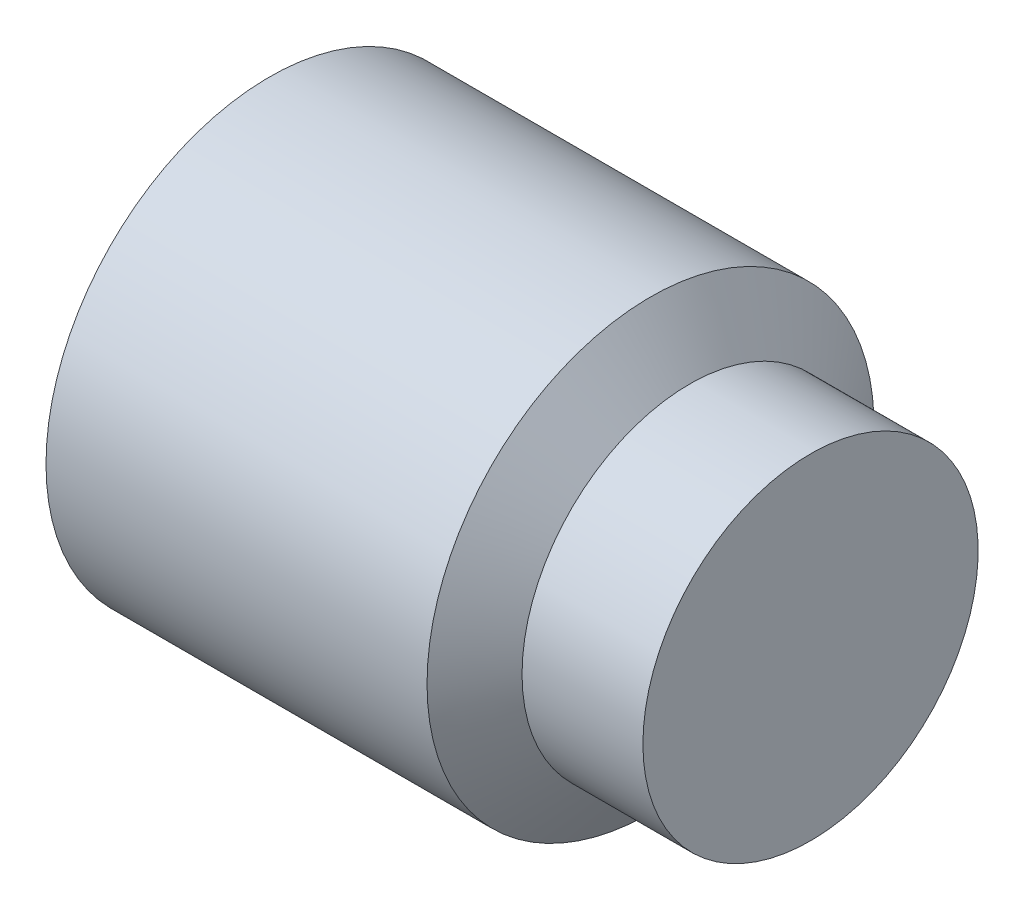
SolidWorks part; units mm, degrees
revolve "BaseBody" add sketch "BodySke" angle 360 about L5 other way angle 60
sketch "BodySke" plane through (0, 0, 0) normal (0, 0, 1) x (1, 0, 0)
  line L0 (0, 0) -> (0, 10.352)
  line L1 (0, 10.352) -> (0.9515, 12)
  line L2 (0.9515, 12) -> (21.4094, 12)
  line L3 (21.4094, 12) -> (23.51, 9)
  line L4 (30, 0) -> (0, 0)
  line L5 (-12.7, 0) -> (88.9, 0) construction
  line L6 (23.51, 9) -> (30, 9)
  line L7 (30, 9) -> (30, 0)
  line L8 (0, -10.352) -> (0.9515, -12) construction
  line L9 (23.51, -9) -> (30, -9) construction
  line L10 (3, 15.875) -> (3, -3.175) construction
  dimension "Length" = 30
  dimension "D1" = 35
  dimension "Diameter" = 24
cosmetic thread "ThreadCosmetic" [suppressed] parameters "Thread_minor"=20.704
ref_plane "Plane1" through (0, 0, 0) normal (0, 0, 1) x (1, 0, 0)
ref_plane "Plane2" through (0, 0, 0) normal (0, 1, 0) x (1, 0, 0)
ref_plane "Plane3" through (0, 0, 0) normal (1, 0, 0) x (0, 0, -1)
sketch "Sketch2" plane through (0, 0, 0) normal (-1, 0, 0) x (0, 0, 1)
  line L0 (3.4641, 6) -> (-3.4641, 6)
  line L1 (-3.4641, 6) -> (-6.9282, 0)
  line L2 (3.4641, 6) -> (6.9282, 0)
  line L3 (3.4641, -6) -> (6.9282, 0)
  line L4 (3.4641, -6) -> (-3.4641, -6)
  line L5 (-3.4641, -6) -> (-6.9282, 0)
  dimension "D2" = 6
  dimension "D3" = 6
extrude "Hex" cut sketch "Sketch2" against normal blind 12
sketch "Sketch4" plane through (0, 4.7709, -0.5249) normal (-1, 0, 0) x (0, 0, 1)
  line L0 (0.5249, -4.7709) -> (8.1959, -4.7709)
  line L1 (0.5249, -4.7709) -> (6.6732, -1.2211) construction
  line L2 (0.5249, -4.7709) -> (4.3604, 1.8724)
  line L3 (6.7899, -3.1774) -> (7.8687, -2.5545)
  line L4 (5.0374, -0.142) -> (6.1162, 0.4809)
  arc A0 (6.7899, -3.1774) -> (5.0374, -0.142) centre (0.5249, -4.7709) ccw
  arc A1 (8.1959, -4.7709) -> (7.8687, -2.5545) centre (0.5249, -4.7709) ccw
  arc A2 (4.3604, 1.8724) -> (6.1162, 0.4809) centre (0.5249, -4.7709) cw
  circle A3 centre (0.5249, -4.7709) radius 6.4645 construction
  circle A4 centre (0.5249, -4.7709) radius 7.671 construction
  dimension "Spline_n_dim" = 12.929
  dimension "Spline_m_dim" = 15.342
  dimension "D1" = 30
  dimension "Spline_p_dim" = 3.505
  dimension "D3" = 1.7525
extrude "Spline6" [suppressed] cut sketch "Sketch4" against normal blind 12
pattern_circular "CirPattern1" [suppressed] count 6 every 60 about axis through (-12.7, 0, 0) along (1, 0, 0)
sketch "Sketch5" plane through (0, 0.4822, 7.7588) normal (-1, 0, 0) x (0, 0, 1)
  line L0 (-7.7588, -0.4822) -> (-0.0878, -0.4822)
  line L1 (-7.7588, -0.4822) -> (-2.7387, 4.538) construction
  line L2 (-7.7588, -0.4822) -> (-7.7588, 7.1888)
  line L3 (-1.9485, 2.8497) -> (-1.2389, 3.5594)
  line L4 (-4.4269, 5.3281) -> (-3.7173, 6.0378)
  line L5 (-4.4269, 5.3281) -> (-1.9485, 2.8497)
  arc A1 (-0.0878, -0.4822) -> (-1.2389, 3.5594) centre (-7.7588, -0.4822) ccw
  arc A2 (-7.7588, 7.1888) -> (-3.7173, 6.0378) centre (-7.7588, -0.4822) cw
  circle A3 centre (-7.7588, -0.4822) radius 6.4645 construction
  circle A4 centre (-7.7588, -0.4822) radius 7.671 construction
  dimension "Spline_n_dim" = 12.929
  dimension "Spline_m_dim" = 15.342
  dimension "Spline_p_dim" = 3.505
  dimension "D3" = 1.7525
  dimension "D1" = 45
  dimension "Spline_a_dim" = 90
extrude "Spline4" [suppressed] cut sketch "Sketch5" against normal blind 12
pattern_circular "CirPattern2" [suppressed] count 4 every 90 about axis through (-12.7, 0, 0) along (1, 0, 0)
sketch "ThdSchSke" plane through (0, 0, 0) normal (0, 0, 1) x (1, 0, 0)
  line L0 (0.9515, -10.352) -> (-0.2025, -12)
  line L1 (0.9515, -10.352) -> (2.1054, -12)
  line L2 (2.1054, -12) -> (2.1054, -15)
  line L3 (-3.175, 0) -> (5.1513, 0) construction
  line L4 (0.9515, 12) -> (0.9515, -12) construction
  line L5 (2.1054, -15) -> (-0.2025, -15)
  line L6 (-0.2025, -15) -> (-0.2025, -12)
  dimension "Thread_minor" = 20.704
  dimension "Diameter" = 24
revolve "ThreadSchematic" [suppressed] cut sketch "ThdSchSke" angle 360 about L3
pattern_linear "ThdSchPat" [suppressed]
equation "\"D2@Sketch2\" = \"Hex_size@Sketch2\" / 2"
equation "\"D3@Sketch2\" = \"Hex_size@Sketch2\" / 2"
equation "\"Thread_minor@ThreadCosmetic\" = \"Minor_dia@BodySke\""
equation "\"D1@Sketch4\" = \"Spline_a_dim@Sketch4\" / 2"
equation "\"D3@Sketch4\" = \"Spline_p_dim@Sketch4\" / 2"
equation "\"D2@CirPattern1\" = \"Spline_a_dim@Sketch4\""
equation "\"Num_teeth@CirPattern1\" = 360 / \"D2@CirPattern1\""
equation "\"Spline_a_dim@Sketch5\" = 90"
equation "\"Spline_p_dim@Sketch5\" = \"Spline_p_dim@Sketch4\""
equation "\"Spline_m_dim@Sketch5\" = \"Spline_m_dim@Sketch4\""
equation "\"Spline_n_dim@Sketch5\" = \"Spline_n_dim@Sketch4\""
equation "\"D1@Sketch5\" = \"Spline_a_dim@Sketch5\" / 2"
equation "\"D3@Sketch5\" = \"Spline_p_dim@Sketch5\" / 2"
equation "\"Key_eng@Spline4\" = \"Key_eng@Spline6\""
equation "\"Thread_minor@ThdSchSke\" = \"Thread_minor@ThreadCosmetic\""
equation "\"Diameter@ThdSchSke\" = \"Diameter@BodySke\""
equation "\"Overcut@ThdSchSke\" = \"Diameter@BodySke\" * 1.25"
equation "\"Num_threads@ThdSchPat\" = int( (\"Length@BodySke\" - ( ( ( \"Diameter@BodySke\" - \"Minor_dia@BodySke\" ) * 0.5 ) / tan( \"Drive_ch_ang@BodySke\" * 0.017453292 ) ) - \"Dog_len@BodySke\" ) / \"Advance@BodySke\" + 0.999 )  + 1"
equation "\"Advance@ThdSchPat\" = (\"Length@BodySke\" - ( ( ( \"Diameter@BodySke\" - \"Minor_dia@BodySke\" ) * 0.5 ) / tan( \"Drive_ch_ang@BodySke\" * 0.017453292 ) ) - \"Dog_len@BodySke\" ) /  (\"Num_threads@ThdSchPat\" - 1) 'relax it"
equation "\"Num_threads@ThdSchPat\" = \"Num_threads@ThdSchPat\" - sgn( \"Num_threads@ThdSchPat\" - 1) '---chamfered tips only---"
